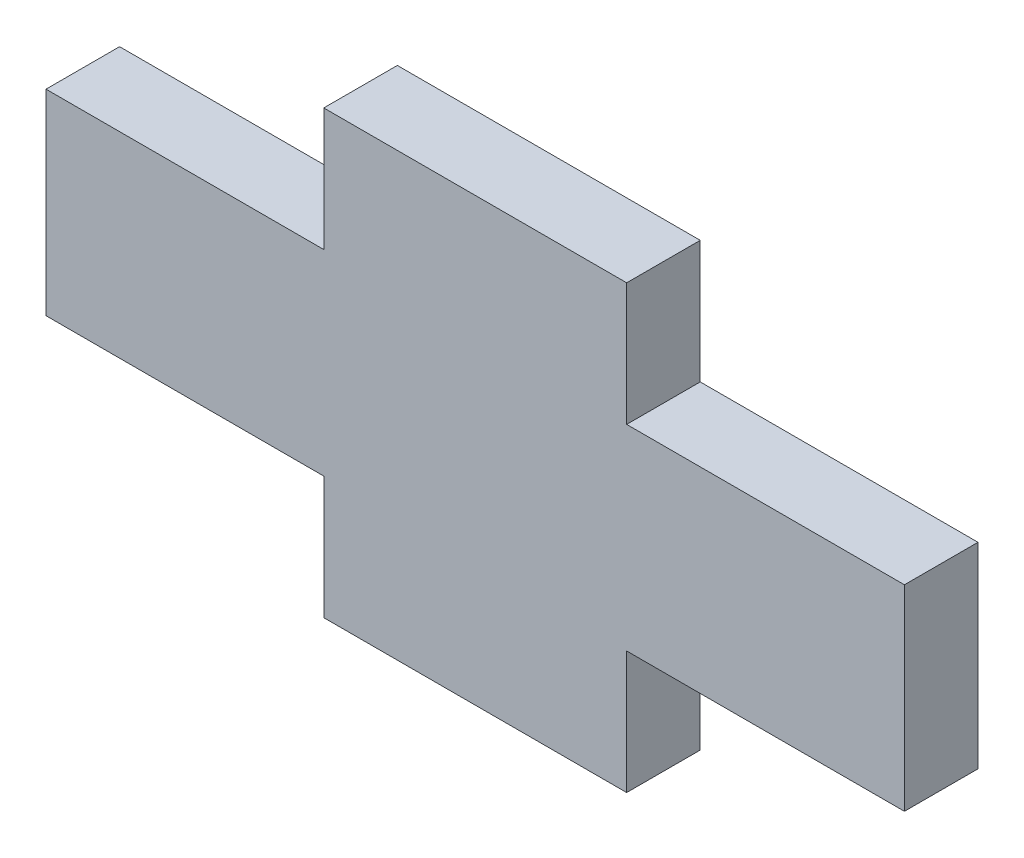
SolidWorks part; units mm, degrees
ref_plane "Płaszczyzna przednia" through (0, 0, 0) normal (0, 0, 1) x (1, 0, 0)
ref_plane "Płaszczyzna górna" through (0, 0, 0) normal (0, 1, 0) x (1, 0, 0)
ref_plane "Płaszczyzna prawa" through (0, 0, 0) normal (1, 0, 0) x (0, 0, -1)
sketch "Szkic1" plane through (0, 0, 0) normal (0, 0, 1) x (1, 0, 0)
  line L0 (-17.5, -4) -> (-17.5, 4)
  line L1 (-6.175, -9) -> (6.175, -9) construction
  line L2 (-6.175, -9) -> (-6.175, 9) construction
  line L3 (-6.175, 9) -> (6.175, 9) construction
  line L4 (6.175, -9) -> (6.175, 9) construction
  line L5 (-6.175, -9) -> (6.175, 9) construction
  line L6 (-6.175, 9) -> (6.175, -9) construction
  line L7 (-17.5, -4) -> (17.5, -4) construction
  line L8 (-17.5, -4) -> (-17.5, 4) construction
  line L9 (-17.5, 4) -> (17.5, 4) construction
  line L10 (17.5, -4) -> (17.5, 4) construction
  line L11 (-17.5, -4) -> (17.5, 4) construction
  line L12 (-17.5, 4) -> (17.5, -4) construction
  line L13 (-17.5, 4) -> (-6.175, 4)
  line L14 (-6.175, 4) -> (-6.175, 9)
  line L15 (-6.175, 9) -> (6.175, 9)
  line L16 (6.175, 9) -> (6.175, 4)
  line L17 (6.175, 4) -> (17.5, 4)
  line L18 (17.5, 4) -> (17.5, -4)
  line L19 (17.5, -4) -> (6.175, -4)
  line L20 (6.175, -4) -> (6.175, -9)
  line L21 (6.175, -9) -> (-6.175, -9)
  line L22 (-6.175, -9) -> (-6.175, -4)
  line L23 (-6.175, -4) -> (-17.5, -4)
  point P0 (0, 0)
  point P6 (0, 0)
  dimension "D1" = 8
  dimension "D2" = 35
  dimension "D3" = 18
  dimension "D4" = 12.35
extrude "Dodanie-wyciągnięcie1" add sketch "Szkic1" along normal mid plane 3
